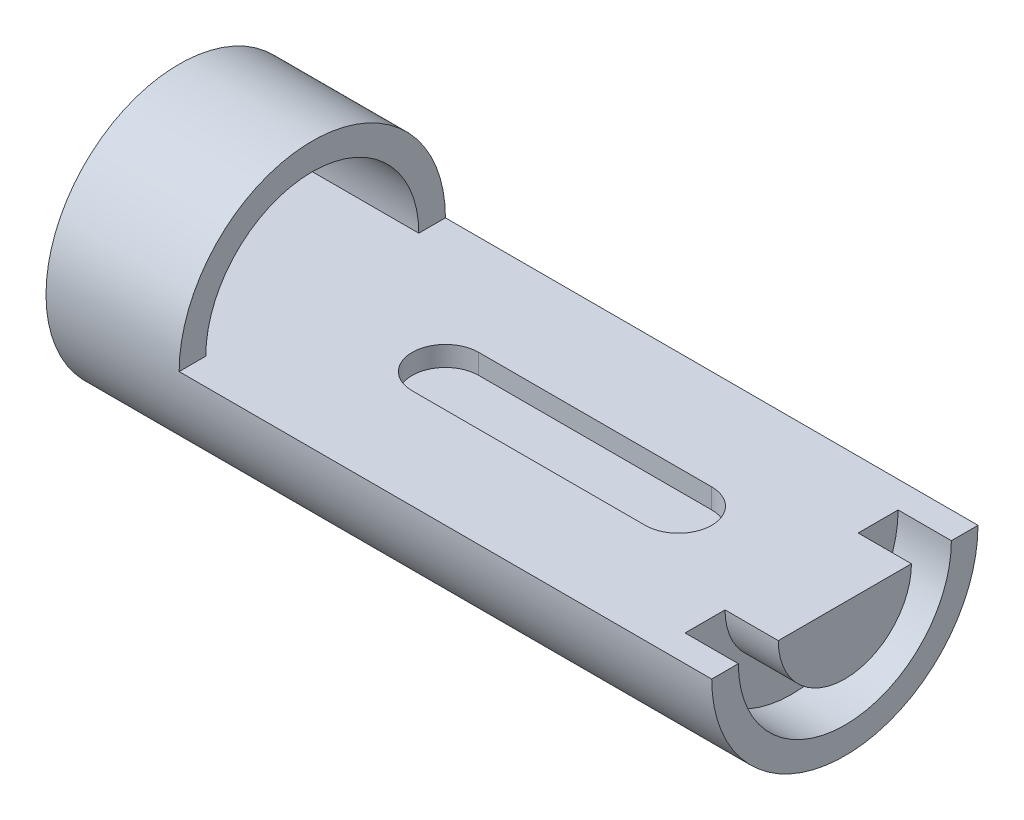
SolidWorks part; units mm, degrees
ref_plane "Front Plane" through (0, 0, 0) normal (0, 0, 1) x (1, 0, 0)
ref_plane "Top Plane" through (0, 0, 0) normal (0, 1, 0) x (1, 0, 0)
ref_plane "Right Plane" through (0, 0, 0) normal (1, 0, 0) x (0, 0, -1)
sketch "Sketch1" plane through (0, 0, 0) normal (1, 0, 0) x (0, 0, -1)
  line L0 (-16, 0) -> (16, 0)
  line L1 (-16, 0) -> (-20, 0)
  line L2 (16, 0) -> (20, 0)
  circle A0 centre (0, 0) radius 20
  circle A1 centre (0, 0) radius 16
  arc A2 (-16, 0) -> (16, 0) centre (0, 0) ccw
  circle A3 centre (0, 0) radius 10
  dimension "D1" = 40
  dimension "D2" = 32
  dimension "D3" = 20
extrude "Boss-Extrude2" add sketch "Sketch1" against normal blind 20 contours A1 L2 A0 L1 | A1 L1 A0 L2 | A3 L0 A1 | L0 A3 region at (0, -4.2441, 0) region at (0, -0.3578, -13) region at (0, 16.4472, 0) region at (0, -0.4472, -18)
extrude "Boss-Extrude3" add sketch "Sketch1<5>" along normal blind 72 contours A3 L0 A1 region at (0, -0.3578, -13)
sketch "Sketch1<5>" plane through (0, 0, 0) normal (1, 0, 0) x (0, 0, -1) same geometry as "Sketch1"
extrude "Boss-Extrude4" add sketch "Sketch1<6>" along normal blind 80 contours L0 A3 | A1 L1 A0 L2 region at (0, -4.2441, 0) region at (0, -0.4472, -18)
sketch "Sketch1<6>" plane through (0, 0, 0) normal (1, 0, 0) x (0, 0, -1) same geometry as "Sketch1"
sketch "Sketch2" plane through (0, 0, 0) normal (0, 1, 0) x (1, 0, 0)
  line L0 (80, -10) -> (80, 10) construction
  line L1 (20, 5) -> (55, 5)
  line L2 (20, -5) -> (55, -5)
  arc A0 (20, 5) -> (20, -5) centre (20, 0) ccw
  arc A1 (55, -5) -> (55, 5) centre (55, 0) ccw
  dimension "D1" = 35
  dimension "D3" = 10
  dimension "D2" = 25
extrude "Cut-Extrude1" cut sketch "Sketch2" against normal blind 3
